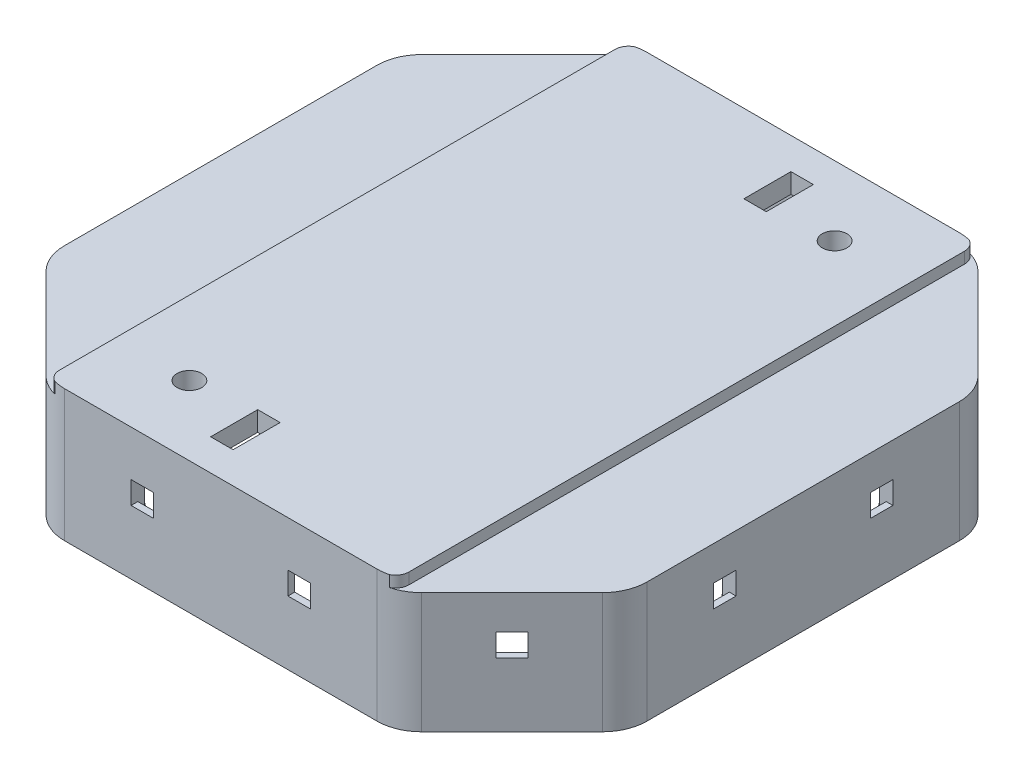
SolidWorks part; units mm, degrees
ref_plane "Front Plane" through (0, 0, 0) normal (0, 0, 1) x (1, 0, 0)
ref_plane "Top Plane" through (0, 0, 0) normal (0, 1, 0) x (1, 0, 0)
ref_plane "Right Plane" through (0, 0, 0) normal (1, 0, 0) x (0, 0, -1)
ref_axis "CenterAxis" through (0, 3.97, 0) along (0, -1, 0)
sketch "Sketch1" plane through (0, 0, 0) normal (0, 1, 0) x (1, 0, 0)
  line L0 (0, 34.664) -> (0, -51.0735) construction
  line L1 (-39, 65) -> (39, 65)
  line L2 (-39, 65) -> (-39, -65)
  line L3 (-39, -65) -> (39, -65)
  line L4 (39, 65) -> (39, -65)
  line L5 (-69.2084, 0) -> (81.5089, 0) construction
  dimension "D1" = 78
  dimension "D2" = 130
extrude "Boss-Extrude1" add sketch "Sketch1" along normal blind 2.5
sketch "Sketch4" plane through (0, 0, 0) normal (0, -1, 0) x (-1, 0, 0)
  line L1 (65, 65) -> (-65, 65)
  line L2 (65, 65) -> (65, -65)
  line L3 (65, -65) -> (-65, -65)
  line L4 (-65, 65) -> (-65, -65)
  line L6 (0, 118.1215) -> (0, -128.1726) construction
  line L7 (153.5171, 0) -> (-213.3352, 0) construction
  dimension "D1" = 130
  dimension "D2" = 130
extrude "Boss-Extrude2" add sketch "Sketch4" along normal blind 1.9
chamfer "Chamfer1" distance 26 angle 45 4 edges at (65, -0.95, 65) (-65, -0.95, 65) (-65, -0.95, -65) (65, -0.95, -65)
sketch "Sketch5" plane through (0, -1.9, 0) normal (0, -1, 0) x (-1, 0, 0)
  line L7 (39, 65) -> (-39, 65) construction
  line L9 (-39, 65) -> (-65, 39) construction
  line L10 (-65, 39) -> (-65, -39) construction
  line L11 (-65, -39) -> (-39, -65) construction
  line L12 (-39, -65) -> (39, -65) construction
  line L13 (39, -65) -> (65, -39) construction
  line L14 (65, -39) -> (65, 39) construction
  line L15 (65, 39) -> (39, 65) construction
  line L16 (39, 65) -> (-39, 65)
  line L17 (-39, 65) -> (-65, 39)
  line L18 (-65, 39) -> (-65, -39)
  line L19 (-65, -39) -> (-39, -65)
  line L20 (-39, -65) -> (39, -65)
  line L21 (39, -65) -> (65, -39)
  line L22 (65, -39) -> (65, 39)
  line L23 (65, 39) -> (39, 65)
  line L24 (37.7574, 62) -> (-37.7574, 62)
  line L25 (-37.7574, 62) -> (-62, 37.7574)
  line L26 (-62, 37.7574) -> (-62, -37.7574)
  line L27 (-62, -37.7574) -> (-37.7574, -62)
  line L28 (-37.7574, -62) -> (37.7574, -62)
  line L29 (37.7574, -62) -> (62, -37.7574)
  line L30 (62, -37.7574) -> (62, 37.7574)
  line L31 (62, 37.7574) -> (37.7574, 62)
  dimension "D1" = 3
extrude "Boss-Extrude3" add sketch "Sketch5" along normal blind 25
sketch "Sketch6" plane through (0, 0, 62) normal (0, 0, -1) x (-1, 0, 0)
  line L0 (0, -73.719) -> (0, 48.5048) construction
  line L1 (-15, -12.65) -> (-20, -12.65)
  line L2 (-15, -12.65) -> (-15, -7.65)
  line L3 (-15, -7.65) -> (-20, -7.65)
  line L4 (-20, -12.65) -> (-20, -7.65)
  line L5 (20, -12.65) -> (15, -12.65)
  line L6 (20, -12.65) -> (20, -7.65)
  line L7 (20, -7.65) -> (15, -7.65)
  line L8 (15, -12.65) -> (15, -7.65)
  line L10 (-37.7574, -1.9) -> (37.7574, -1.9) construction
  dimension "D1" = 5
  dimension "D2" = 5
  dimension "D3" = 5
  dimension "D4" = 5
  dimension "D5" = 30
  dimension "D6" = 5.75
  dimension "D7" = 5.75
extrude "Cut-Extrude3" cut sketch "Sketch6" against normal up to next
sketch "Sketch13" plane through (-49.8787, 0, 49.8787) normal (0.7071, 0, -0.7071) x (-0.7071, 0, -0.7071)
  line L0 (-17.1421, -1.9) -> (17.1421, -1.9) construction
  line L1 (2.5, -12.65) -> (-2.5, -12.65)
  line L2 (2.5, -12.65) -> (2.5, -7.65)
  line L3 (2.5, -7.65) -> (-2.5, -7.65)
  line L4 (-2.5, -12.65) -> (-2.5, -7.65)
  line L5 (0, -31.7169) -> (0, 9.0748) construction
  line L6 (-17.1421, -26.9) -> (-17.1421, -1.9) construction
  line L7 (17.1421, -26.9) -> (17.1421, -1.9) construction
  dimension "D1" = 5
  dimension "D2" = 5
  dimension "D3" = 5.75
extrude "Cut-Extrude6" cut sketch "Sketch13" against normal up to next
sketch "Sketch9" plane through (0, 0, 62) normal (0, 0, -1) x (-1, 0, 0)
  line L0 (39.1927, -10.15) -> (-34.1415, -10.15) construction
  line L4 (20, -18.4) -> (7.35, -18.4)
  line L5 (20, -18.4) -> (20, -1.9)
  line L6 (20, -1.9) -> (7.35, -1.9)
  line L7 (7.35, -18.4) -> (7.35, -1.9)
  line L10 (-20, -18.4) -> (-7.35, -18.4)
  line L11 (-20, -18.4) -> (-20, -1.9)
  line L12 (-20, -1.9) -> (-7.35, -1.9)
  line L13 (-7.35, -18.4) -> (-7.35, -1.9)
  line L18 (-37.7574, -1.9) -> (37.7574, -1.9) construction
  line L19 (20, -12.65) -> (20, -7.65) construction
  line L20 (-20, -7.65) -> (-20, -12.65) construction
  line L21 (20, -7.65) -> (15, -7.65) construction
  line L22 (15, -12.65) -> (20, -12.65) construction
  dimension "D1" = 12.65
  dimension "D2" = 12.65
extrude "Cut-Extrude5" cut sketch "Sketch9" against normal blind 1.5
sketch "Sketch14" plane through (-49.8787, 0, 49.8787) normal (0.7071, 0, -0.7071) x (-0.7071, 0, -0.7071)
  line L0 (-17.1421, -1.9) -> (17.1421, -1.9) construction
  line L1 (2.5, -1.9) -> (-10.15, -1.9)
  line L2 (2.5, -1.9) -> (2.5, -18.4)
  line L3 (2.5, -18.4) -> (-10.15, -18.4)
  line L4 (-10.15, -1.9) -> (-10.15, -18.4)
  line L5 (2.5, -12.65) -> (2.5, -7.65) construction
  line L6 (10.5909, -10.15) -> (-6.85, -10.15) construction
  line L7 (2.5, -7.65) -> (-2.5, -7.65) construction
  line L8 (-2.5, -12.65) -> (2.5, -12.65) construction
  dimension "D1" = 12.65
extrude "Cut-Extrude7" cut sketch "Sketch14" against normal blind 1.5
sketch "Sketch10" plane through (0, 0, 62) normal (0, 0, -1) x (-1, 0, 0)
  line L0 (45.2947, -10.154) -> (11.3128, -10.154) construction
  line L4 (7.35, -18.4) -> (5.35, -18.4)
  line L5 (7.35, -18.4) -> (7.35, -1.9)
  line L6 (7.35, -1.9) -> (5.35, -1.9)
  line L7 (5.35, -18.4) -> (5.35, -1.9)
  line L8 (-7.35, -1.9) -> (7.35, -1.9) construction
  line L9 (-7.35, -18.4) -> (-5.35, -18.4)
  line L10 (-7.35, -18.4) -> (-7.35, -1.9)
  line L11 (-7.35, -1.9) -> (-5.35, -1.9)
  line L12 (-5.35, -18.4) -> (-5.35, -1.9)
  circle A0 centre (22.59, -15.869) radius 1
  circle A1 centre (22.59, -4.439) radius 1
  circle A2 centre (-22.59, -15.869) radius 1
  circle A3 centre (-22.59, -4.439) radius 1
  dimension "D1" = 2
  dimension "D2" = 2
  dimension "D3" = 2
  dimension "D4" = 2
  dimension "D5" = 11.43
  dimension "D6" = 11.43
  dimension "D7" = 8.254
  dimension "D8" = 15.24
  dimension "D9" = 2
  dimension "D10" = 2
  dimension "D11" = 15.24
extrude "Boss-Extrude5" add sketch "Sketch10" along normal blind 1.75
sketch "Sketch15" plane through (-49.8787, 0, 49.8787) normal (0.7071, 0, -0.7071) x (-0.7071, 0, -0.7071)
  line L0 (-17.1421, -1.9) -> (-10.15, -1.9) construction
  line L1 (-10.15, -18.4) -> (-12.15, -18.4)
  line L2 (-10.15, -18.4) -> (-10.15, -1.9)
  line L3 (-10.15, -1.9) -> (-12.15, -1.9)
  line L4 (-12.15, -18.4) -> (-12.15, -1.9)
  line L5 (11.6969, -10.15) -> (-6.9983, -10.15) construction
  line L6 (-2.5, -12.65) -> (2.5, -12.65) construction
  line L7 (2.5, -7.65) -> (-2.5, -7.65) construction
  circle A0 centre (5.09, -15.865) radius 1
  circle A1 centre (5.09, -4.435) radius 1
  dimension "D2" = 2
  dimension "D3" = 2
  dimension "D1" = 2
  dimension "D4" = 15.24
  dimension "D5" = 11.43
extrude "Boss-Extrude9" add sketch "Sketch15" along normal blind 1.75
sketch "Sketch12" plane through (0, -1.9, 0) normal (0, -1, 0) x (-1, 0, 0)
  line L0 (92.5171, 0) -> (-110.2203, 0) construction
  line L1 (32.5, -55) -> (27.5, -55)
  line L2 (32.5, -55) -> (32.5, -50)
  line L3 (32.5, -50) -> (27.5, -50)
  line L4 (27.5, -55) -> (27.5, -50)
  line L5 (0, -112.6882) -> (0, 159.7855) construction
  line L6 (-32.5, -55) -> (-27.5, -55)
  line L7 (-32.5, -55) -> (-32.5, -50)
  line L8 (-32.5, -50) -> (-27.5, -50)
  line L9 (-27.5, -55) -> (-27.5, -50)
  dimension "D1" = 5
  dimension "D2" = 5
  dimension "D3" = 50
  dimension "D4" = 27.5
extrude "Boss-Extrude8" [suppressed] add sketch "Sketch12" along normal blind 10
fillet "Fillet4" [suppressed] radius 1
sketch "Sketch16" plane through (-62, 0, 0) normal (1, 0, 0) x (0, 0, -1)
  line L0 (0, -45.9705) -> (0, 131.7483) construction
  line L1 (20, -12.65) -> (15, -12.65)
  line L2 (20, -12.65) -> (20, -7.65)
  line L3 (20, -7.65) -> (15, -7.65)
  line L4 (15, -12.65) -> (15, -7.65)
  line L5 (-15, -12.65) -> (-20, -12.65)
  line L6 (-15, -12.65) -> (-15, -7.65)
  line L7 (-15, -7.65) -> (-20, -7.65)
  line L8 (-20, -12.65) -> (-20, -7.65)
  line L9 (37.7574, -26.9) -> (37.7574, -1.9) construction
  line L10 (-37.7574, -26.9) -> (-37.7574, -1.9) construction
  line L11 (-37.7574, -1.9) -> (37.7574, -1.9) construction
  dimension "D1" = 30
  dimension "D2" = 5
  dimension "D3" = 5
  dimension "D4" = 5
  dimension "D5" = 5
  dimension "D6" = 5.75
  dimension "D7" = 5.75
extrude "Cut-Extrude8" cut sketch "Sketch16" against normal up to next
sketch "Sketch17" plane through (-62, 0, 0) normal (1, 0, 0) x (0, 0, -1)
  line L0 (20, -12.65) -> (20, -7.65) construction
  line L1 (-15, -18.4) -> (-27.65, -18.4)
  line L2 (-15, -18.4) -> (-15, -1.9)
  line L3 (-15, -1.9) -> (-27.65, -1.9)
  line L4 (-27.65, -18.4) -> (-27.65, -1.9)
  line L5 (20, -18.4) -> (7.35, -18.4)
  line L6 (20, -18.4) -> (20, -1.9)
  line L7 (20, -1.9) -> (7.35, -1.9)
  line L8 (7.35, -18.4) -> (7.35, -1.9)
  line L9 (-37.7574, -1.9) -> (37.7574, -1.9) construction
  line L10 (-15, -12.65) -> (-15, -7.65) construction
  line L11 (27.4384, -10.15) -> (-34.0605, -10.15) construction
  line L12 (15, -12.65) -> (20, -12.65) construction
  line L13 (20, -7.65) -> (15, -7.65) construction
  dimension "D1" = 12.65
  dimension "D2" = 12.65
extrude "Cut-Extrude9" cut sketch "Sketch17" against normal blind 1.5
sketch "Sketch18" plane through (-62, 0, 0) normal (1, 0, 0) x (0, 0, -1)
  line L0 (32.9525, -10.15) -> (-38.3333, -10.15) construction
  line L1 (20, -12.65) -> (15, -12.65) construction
  line L2 (15, -7.65) -> (20, -7.65) construction
  line L3 (7.35, -1.9) -> (7.35, -18.4) construction
  line L4 (-27.65, -1.9) -> (-27.65, -18.4) construction
  line L5 (-15, -1.9) -> (7.35, -1.9) construction
  line L6 (7.35, -18.4) -> (5.35, -18.4)
  line L7 (7.35, -18.4) -> (7.35, -1.9)
  line L8 (7.35, -1.9) -> (5.35, -1.9)
  line L9 (5.35, -18.4) -> (5.35, -1.9)
  line L10 (-37.7574, -1.9) -> (-27.65, -1.9) construction
  line L11 (-27.65, -18.4) -> (-29.65, -18.4)
  line L12 (-27.65, -18.4) -> (-27.65, -1.9)
  line L13 (-27.65, -1.9) -> (-29.65, -1.9)
  line L14 (-29.65, -18.4) -> (-29.65, -1.9)
  circle A0 centre (22.59, -15.865) radius 1
  circle A1 centre (22.59, -4.435) radius 1
  circle A2 centre (-12.41, -15.865) radius 1
  circle A3 centre (-12.41, -4.435) radius 1
  dimension "D3" = 2
  dimension "D4" = 2
  dimension "D5" = 2
  dimension "D6" = 2
  dimension "D1" = 11.43
  dimension "D2" = 11.43
  dimension "D7" = 15.24
  dimension "D8" = 15.24
  dimension "D9" = 2
  dimension "D10" = 2
extrude "Boss-Extrude10" add sketch "Sketch18" along normal blind 1.75
sketch "Sketch19" plane through (49.8787, 0, 49.8787) normal (-0.7071, 0, -0.7071) x (-0.7071, 0, 0.7071)
  line L0 (0, -22.7201) -> (0, -10.1184) construction
  line L3 (17.1421, -26.9) -> (17.1421, -1.9) construction
  line L4 (-17.1421, -26.9) -> (-17.1421, -1.9) construction
  line L5 (-17.1421, -1.9) -> (17.1421, -1.9) construction
  line L6 (2.5, -12.65) -> (-2.5, -12.65)
  line L7 (2.5, -12.65) -> (2.5, -7.65)
  line L8 (2.5, -7.65) -> (-2.5, -7.65)
  line L9 (-2.5, -12.65) -> (-2.5, -7.65)
  dimension "D1" = 5
  dimension "D2" = 5
  dimension "D3" = 5.75
extrude "Cut-Extrude10" cut sketch "Sketch19" against normal up to next
sketch "Sketch20" plane through (49.8787, 0, 49.8787) normal (-0.7071, 0, -0.7071) x (-0.7071, 0, 0.7071)
  line L0 (-17.1421, -1.9) -> (17.1421, -1.9) construction
  line L1 (10.15, -18.4) -> (-2.5, -18.4)
  line L2 (10.15, -18.4) -> (10.15, -1.9)
  line L3 (10.15, -1.9) -> (-2.5, -1.9)
  line L4 (-2.5, -18.4) -> (-2.5, -1.9)
  line L5 (-2.5, -7.65) -> (-2.5, -12.65) construction
  line L6 (13.9228, -10.15) -> (-12.316, -10.15) construction
  line L7 (-2.5, -12.65) -> (2.5, -12.65) construction
  line L8 (2.5, -7.65) -> (-2.5, -7.65) construction
  dimension "D1" = 12.65
extrude "Cut-Extrude11" cut sketch "Sketch20" against normal blind 1.5
sketch "Sketch21" plane through (49.8787, 0, 49.8787) normal (-0.7071, 0, -0.7071) x (-0.7071, 0, 0.7071)
  line L0 (15.0556, -10.15) -> (-12.6108, -10.15) construction
  line L1 (12.15, -18.4) -> (10.15, -18.4)
  line L2 (12.15, -18.4) -> (12.15, -1.9)
  line L3 (12.15, -1.9) -> (10.15, -1.9)
  line L4 (10.15, -18.4) -> (10.15, -1.9)
  line L5 (2.5, -12.65) -> (-2.5, -12.65) construction
  line L6 (-2.5, -7.65) -> (2.5, -7.65) construction
  line L7 (10.15, -1.9) -> (17.1421, -1.9) construction
  circle A0 centre (-5.09, -15.865) radius 1
  circle A1 centre (-5.09, -4.435) radius 1
  dimension "D1" = 2
  dimension "D2" = 2
  dimension "D3" = 2
  dimension "D4" = 15.24
  dimension "D5" = 11.43
extrude "Boss-Extrude11" add sketch "Sketch21" along normal blind 1.75
sketch "Sketch22" plane through (62, 0, 0) normal (-1, 0, 0) x (0, 0, 1)
  line L0 (0, -48.3456) -> (0, 13.9543) construction
  line L1 (20, -12.65) -> (15, -12.65)
  line L2 (20, -12.65) -> (20, -7.65)
  line L3 (20, -7.65) -> (15, -7.65)
  line L4 (15, -12.65) -> (15, -7.65)
  line L5 (-15, -12.65) -> (-20, -12.65)
  line L6 (-15, -12.65) -> (-15, -7.65)
  line L7 (-15, -7.65) -> (-20, -7.65)
  line L8 (-20, -12.65) -> (-20, -7.65)
  line L9 (37.7574, -26.9) -> (37.7574, -1.9) construction
  line L10 (-37.7574, -26.9) -> (-37.7574, -1.9) construction
  line L12 (-37.7574, -1.9) -> (37.7574, -1.9) construction
  dimension "D1" = 5
  dimension "D2" = 5
  dimension "D3" = 5
  dimension "D4" = 5
  dimension "D5" = 5.75
  dimension "D6" = 5.75
  dimension "D7" = 30
extrude "Cut-Extrude12" cut sketch "Sketch22" against normal up to next
sketch "Sketch23" plane through (62, 0, 0) normal (-1, 0, 0) x (0, 0, 1)
  line L1 (27.65, -18.4) -> (15, -18.4)
  line L2 (27.65, -18.4) -> (27.65, -1.9)
  line L3 (27.65, -1.9) -> (15, -1.9)
  line L4 (15, -18.4) -> (15, -1.9)
  line L5 (-7.35, -18.4) -> (-20, -18.4)
  line L6 (-7.35, -18.4) -> (-7.35, -1.9)
  line L7 (-7.35, -1.9) -> (-20, -1.9)
  line L8 (-20, -18.4) -> (-20, -1.9)
  line L10 (-37.7574, -1.9) -> (37.7574, -1.9) construction
  line L11 (30.5276, -10.15) -> (-34.6722, -10.15) construction
  line L12 (20, -7.65) -> (15, -7.65) construction
  line L13 (15, -12.65) -> (20, -12.65) construction
  line L14 (15, -7.65) -> (15, -12.65) construction
  line L15 (-20, -7.65) -> (-20, -12.65) construction
  dimension "D1" = 12.65
  dimension "D2" = 12.65
extrude "Cut-Extrude13" cut sketch "Sketch23" against normal blind 1.5
sketch "Sketch24" plane through (62, 0, 0) normal (-1, 0, 0) x (0, 0, 1)
  line L0 (29.9106, -10.15) -> (-34.7522, -10.15) construction
  line L1 (29.65, -18.4) -> (27.65, -18.4)
  line L2 (29.65, -18.4) -> (29.65, -1.9)
  line L3 (29.65, -1.9) -> (27.65, -1.9)
  line L4 (27.65, -18.4) -> (27.65, -1.9)
  line L5 (-5.35, -18.4) -> (-7.35, -18.4)
  line L6 (-5.35, -18.4) -> (-5.35, -1.9)
  line L7 (-5.35, -1.9) -> (-7.35, -1.9)
  line L8 (-7.35, -18.4) -> (-7.35, -1.9)
  line L9 (20, -12.65) -> (15, -12.65) construction
  line L10 (15, -7.65) -> (20, -7.65) construction
  line L11 (-7.35, -1.9) -> (15, -1.9) construction
  line L12 (27.65, -1.9) -> (37.7574, -1.9) construction
  circle A0 centre (12.41, -15.865) radius 1
  circle A1 centre (12.41, -4.435) radius 1
  circle A2 centre (-22.59, -15.865) radius 1
  circle A3 centre (-22.59, -4.435) radius 1
  dimension "D1" = 2
  dimension "D2" = 2
  dimension "D3" = 2
  dimension "D4" = 2
  dimension "D5" = 2
  dimension "D6" = 2
  dimension "D7" = 15.24
  dimension "D8" = 15.24
  dimension "D9" = 11.43
  dimension "D10" = 11.43
extrude "Boss-Extrude12" add sketch "Sketch24" along normal blind 1.75
sketch "Sketch27" plane through (0, -1.9, 0) normal (0, -1, 0) x (-1, 0, 0)
  line L0 (-25.75, 57) -> (-9.25, 57)
  line L3 (37.7574, 62) -> (-37.7574, 62) construction
  line L4 (-9.25, 62) -> (-25.75, 62)
  line L5 (25.75, 62) -> (25.75, 57)
  line L6 (-9.25, 62) -> (-9.25, 57)
  line L7 (-25.75, 57) -> (-25.75, 62)
  line L8 (9.25, 62) -> (9.25, 57)
  line L9 (9.25, 57) -> (25.75, 57)
  line L10 (9.25, 62) -> (25.75, 62)
  line L11 (0, 103.5595) -> (0, 19.1897) construction
  dimension "D1" = 16.5
  dimension "D2" = 18.5
  dimension "D4" = 16.5
  dimension "D5" = 5
  dimension "D6" = 5
extrude "Cut-Extrude16" cut sketch "Sketch27" against normal up to surface (1.9 mm away) up to face at (-52, 0, -22.75)
sketch "Sketch32" plane through (0, 0, -62) normal (0, 0, 1) x (1, 0, 0)
  line L0 (0, -56.2842) -> (0, 5.1948) construction
  line L1 (20, -12.65) -> (15, -12.65)
  line L2 (20, -12.65) -> (20, -7.65)
  line L3 (20, -7.65) -> (15, -7.65)
  line L4 (15, -12.65) -> (15, -7.65)
  line L5 (-15, -12.65) -> (-20, -12.65)
  line L6 (-15, -12.65) -> (-15, -7.65)
  line L7 (-15, -7.65) -> (-20, -7.65)
  line L8 (-20, -12.65) -> (-20, -7.65)
  line L9 (-37.7574, -26.9) -> (-37.7574, -1.9) construction
  line L10 (37.7574, -26.9) -> (37.7574, -1.9) construction
  line L11 (-37.7574, 0) -> (37.7574, 0) construction
  dimension "D1" = 5
  dimension "D2" = 5
  dimension "D3" = 5
  dimension "D4" = 5
  dimension "D5" = 30
  dimension "D6" = 7.65
  dimension "D7" = 7.65
extrude "Cut-Extrude20" cut sketch "Sketch32" against normal up to next
sketch "Sketch33" plane through (0, 0, -62) normal (0, 0, 1) x (1, 0, 0)
  line L0 (15, -12.65) -> (20, -12.65) construction
  line L1 (25.75, -12.65) -> (9.25, -12.65)
  line L2 (25.75, -12.65) -> (25.75, 0)
  line L3 (25.75, 0) -> (9.25, 0)
  line L4 (9.25, -12.65) -> (9.25, 0)
  line L5 (17.5, -39.4676) -> (17.5, 3.7001) construction
  line L6 (-17.5, -41.1802) -> (-17.5, 6.7675) construction
  line L7 (15, -7.65) -> (15, -12.65) construction
  line L8 (20, -12.65) -> (20, -7.65) construction
  line L9 (-15, -12.65) -> (-15, -7.65) construction
  line L10 (-20, -7.65) -> (-20, -12.65) construction
  line L11 (-20, -12.65) -> (-15, -12.65) construction
  line L12 (-9.25, -12.65) -> (-25.75, -12.65)
  line L13 (-9.25, -12.65) -> (-9.25, 0)
  line L14 (-9.25, 0) -> (-25.75, 0)
  line L15 (-25.75, -12.65) -> (-25.75, 0)
  dimension "D1" = 12.65
  dimension "D2" = 16.5
  dimension "D3" = 12.65
  dimension "D4" = 16.5
extrude "Cut-Extrude21" cut sketch "Sketch33" against normal blind 1.5
sketch "Sketch34" plane through (0, 0, -62) normal (0, 0, 1) x (1, 0, 0)
  line L0 (17.5, 6.692) -> (17.5, -45.6178) construction
  line L1 (20, -7.65) -> (20, -12.65) construction
  line L2 (15, -12.65) -> (15, -7.65) construction
  line L4 (-17.5, -39.3596) -> (-17.5, 3.7236) construction
  line L5 (-15, -7.65) -> (-15, -12.65) construction
  line L6 (-20, -12.65) -> (-20, -7.65) construction
  line L10 (25.75, 0) -> (9.25, 0) construction
  line L11 (-9.25, 0) -> (-25.75, 0) construction
  circle A0 centre (23.215, -15.24) radius 1
  circle A1 centre (11.785, -15.24) radius 1
  circle A2 centre (-11.785, -15.24) radius 1
  circle A3 centre (-23.215, -15.24) radius 1
  dimension "D1" = 2
  dimension "D2" = 2
  dimension "D5" = 2
  dimension "D6" = 2
  dimension "D3" = 11.43
  dimension "D4" = 15.24
  dimension "D7" = 11.43
  dimension "D8" = 15.24
extrude "Boss-Extrude14" add sketch "Sketch34" along normal blind 1.75
sketch "Sketch35" plane through (49.8787, 0, -49.8787) normal (-0.7071, 0, 0.7071) x (0.7071, 0, 0.7071)
  line L0 (-17.1421, -1.9) -> (17.1421, -1.9) construction
  line L1 (2.5, -12.65) -> (-2.5, -12.65)
  line L2 (2.5, -12.65) -> (2.5, -7.65)
  line L3 (2.5, -7.65) -> (-2.5, -7.65)
  line L4 (-2.5, -12.65) -> (-2.5, -7.65)
  line L5 (0, -41.1131) -> (0, 9.0774) construction
  line L6 (17.1421, -26.9) -> (17.1421, -1.9) construction
  line L7 (-17.1421, -26.9) -> (-17.1421, -1.9) construction
  dimension "D1" = 5
  dimension "D2" = 5
  dimension "D3" = 5.75
extrude "Cut-Extrude22" cut sketch "Sketch35" against normal up to next
sketch "Sketch36" plane through (49.8787, 0, -49.8787) normal (-0.7071, 0, 0.7071) x (0.7071, 0, 0.7071)
  line L0 (-2.5, -7.65) -> (-2.5, -12.65) construction
  line L1 (10.15, -1.9) -> (-2.5, -1.9)
  line L2 (10.15, -1.9) -> (10.15, -18.4)
  line L3 (10.15, -18.4) -> (-2.5, -18.4)
  line L4 (-2.5, -1.9) -> (-2.5, -18.4)
  line L5 (14.9901, -10.15) -> (-10.7496, -10.15) construction
  line L6 (-2.5, -12.65) -> (2.5, -12.65) construction
  line L7 (2.5, -7.65) -> (-2.5, -7.65) construction
  line L8 (-17.1421, -1.9) -> (17.1421, -1.9) construction
  dimension "D1" = 12.65
extrude "Cut-Extrude23" cut sketch "Sketch36" against normal blind 1.5
sketch "Sketch37" plane through (49.8787, 0, -49.8787) normal (-0.7071, 0, 0.7071) x (0.7071, 0, 0.7071)
  line L0 (10.15, -1.9) -> (17.1421, -1.9) construction
  line L1 (10.15, -18.4) -> (12.15, -18.4)
  line L2 (10.15, -18.4) -> (10.15, -1.9)
  line L3 (10.15, -1.9) -> (12.15, -1.9)
  line L4 (12.15, -18.4) -> (12.15, -1.9)
  line L5 (15.4954, -10.15) -> (-15.257, -10.15) construction
  line L6 (2.5, -7.65) -> (-2.5, -7.65) construction
  line L7 (-2.5, -12.65) -> (2.5, -12.65) construction
  circle A0 centre (-5.09, -15.865) radius 1
  circle A1 centre (-5.09, -4.435) radius 1
  dimension "D2" = 2
  dimension "D3" = 2
  dimension "D1" = 2
  dimension "D4" = 11.43
  dimension "D5" = 15.24
extrude "Boss-Extrude15" add sketch "Sketch37" along normal blind 1.75
fillet "Fillet5" radius 3 4 edges tangent propagation no
sketch "Sketch38" plane through (-49.8787, 0, -49.8787) normal (0.7071, 0, 0.7071) x (0.7071, 0, -0.7071)
  line L0 (0, -45.2412) -> (0, 20.7133) construction
  line L1 (-17.1421, -26.9) -> (-17.1421, -1.9) construction
  line L2 (17.1421, -26.9) -> (17.1421, -1.9) construction
  line L3 (-17.1421, -1.9) -> (17.1421, -1.9) construction
  line L4 (2.5, -12.65) -> (-2.5, -12.65)
  line L5 (2.5, -12.65) -> (2.5, -7.65)
  line L6 (2.5, -7.65) -> (-2.5, -7.65)
  line L7 (-2.5, -12.65) -> (-2.5, -7.65)
  dimension "D1" = 5
  dimension "D2" = 5
  dimension "D3" = 5.75
extrude "Cut-Extrude24" cut sketch "Sketch38" against normal up to next contours L6 L7 L4 L5
sketch "Sketch39" plane through (-49.8787, 0, -49.8787) normal (0.7071, 0, 0.7071) x (0.7071, 0, -0.7071)
  line L0 (2.5, -12.65) -> (2.5, -7.65) construction
  line L1 (2.5, -18.4) -> (-10.15, -18.4)
  line L2 (2.5, -18.4) -> (2.5, -1.9)
  line L3 (2.5, -1.9) -> (-10.15, -1.9)
  line L4 (-10.15, -18.4) -> (-10.15, -1.9)
  line L5 (-17.1421, -1.9) -> (17.1421, -1.9) construction
  line L6 (7.9642, -10.15) -> (-14.3354, -10.15) construction
  line L7 (2.5, -7.65) -> (-2.5, -7.65) construction
  line L8 (2.5, -12.65) -> (-2.5, -12.65) construction
  dimension "D1" = 12.65
extrude "Cut-Extrude25" cut sketch "Sketch39" against normal blind 1.5
sketch "Sketch40" plane through (-49.8787, 0, -49.8787) normal (0.7071, 0, 0.7071) x (0.7071, 0, -0.7071)
  line L0 (-17.1421, -1.9) -> (-10.15, -1.9) construction
  line L1 (-10.15, -18.4) -> (-12.15, -18.4)
  line L2 (-10.15, -18.4) -> (-10.15, -1.9)
  line L3 (-10.15, -1.9) -> (-12.15, -1.9)
  line L4 (-12.15, -18.4) -> (-12.15, -1.9)
  line L5 (11.3212, -10.15) -> (-14.9762, -10.15) construction
  line L6 (-2.5, -12.65) -> (2.5, -12.65) construction
  line L7 (-2.5, -7.65) -> (2.5, -7.65) construction
  circle A0 centre (5.09, -15.865) radius 1
  circle A1 centre (5.09, -4.435) radius 1
  dimension "D2" = 2
  dimension "D3" = 2
  dimension "D1" = 2
  dimension "D4" = 11.43
  dimension "D5" = 15.24
extrude "Boss-Extrude16" add sketch "Sketch40" along normal blind 1.75
fillet "Fillet6" radius 10 8 edges at (-65, -13.45, -39) (65, -13.45, -39) (65, -13.45, 39) (-65, -13.45, 39)
sketch "Sketch41" plane through (0, -1.9, 0) normal (0, -1, 0) x (-1, 0, 0)
  line L0 (-49.9494, -39.5549) -> (-51.7172, -37.7872)
  line L1 (-51.7172, -37.7872) -> (-49.9494, -36.0194)
  line L2 (-49.9494, -36.0194) -> (-48.1816, -37.7872)
  line L3 (-48.1816, -37.7872) -> (-49.9494, -39.5549)
  line L4 (-43.7622, -58.1165) -> (-41.4641, -55.8184) construction
  line L5 (-40.0499, -57.2326) -> (-41.4641, -55.8184) construction
  line L6 (37.7872, 51.7172) -> (39.5549, 49.9494)
  line L7 (-27.35, -52.25) -> (-24.85, -52.25)
  line L8 (-27.35, -52.25) -> (-27.35, -54.75)
  line L9 (-27.35, -54.75) -> (-24.85, -54.75)
  line L10 (-24.85, -52.25) -> (-24.85, -54.75)
  line L11 (24.85, -52.25) -> (27.35, -52.25)
  line L12 (24.85, -52.25) -> (24.85, -54.75)
  line L13 (24.85, -54.75) -> (27.35, -54.75)
  line L14 (27.35, -52.25) -> (27.35, -54.75)
  line L15 (52.25, -7.65) -> (54.75, -7.65)
  line L16 (52.25, -7.65) -> (52.25, -10.15)
  line L17 (52.25, -10.15) -> (54.75, -10.15)
  line L18 (54.75, -7.65) -> (54.75, -10.15)
  line L19 (52.25, 27.35) -> (54.75, 27.35)
  line L20 (52.25, 27.35) -> (52.25, 24.85)
  line L21 (52.25, 24.85) -> (54.75, 24.85)
  line L22 (54.75, 27.35) -> (54.75, 24.85)
  line L23 (-54.75, -7.65) -> (-52.25, -7.65)
  line L24 (-54.75, -7.65) -> (-54.75, -10.15)
  line L25 (-54.75, -10.15) -> (-52.25, -10.15)
  line L26 (-52.25, -7.65) -> (-52.25, -10.15)
  line L27 (-54.75, 27.35) -> (-52.25, 27.35)
  line L28 (-54.75, 27.35) -> (-54.75, 24.85)
  line L29 (-54.75, 24.85) -> (-52.25, 24.85)
  line L30 (-52.25, 27.35) -> (-52.25, 24.85)
  line L31 (39.5549, 49.9494) -> (37.7872, 48.1816)
  line L32 (37.7872, 48.1816) -> (36.0194, 49.9494)
  line L33 (36.0194, 49.9494) -> (37.7872, 51.7172)
  line L34 (-39.5549, 49.9494) -> (-37.7872, 48.1816)
  line L35 (-37.7872, 48.1816) -> (-36.0194, 49.9494)
  line L36 (-36.0194, 49.9494) -> (-37.7872, 51.7172)
  line L37 (-37.7872, 51.7172) -> (-39.5549, 49.9494)
  line L38 (-5.35, -60.25) -> (-7.35, -60.25) construction
  line L39 (-7.35, -63.5) -> (-7.35, -60.25) construction
  line L40 (7.35, -60.25) -> (7.35, -62) construction
  line L41 (5.35, -60.25) -> (7.35, -60.25) construction
  line L42 (51.7172, -37.7872) -> (49.9494, -39.5549)
  line L43 (49.9494, -39.5549) -> (48.1816, -37.7872)
  line L44 (48.1816, -37.7872) -> (49.9494, -36.0194)
  line L45 (49.9494, -36.0194) -> (51.7172, -37.7872)
  line L48 (41.4641, -55.8184) -> (40.0499, -57.2326) construction
  line L49 (43.7622, -58.1165) -> (41.4641, -55.8184) construction
  line L50 (-60.25, -27.65) -> (-62, -27.65) construction
  line L51 (-60.25, -29.65) -> (-60.25, -27.65) construction
  line L52 (-60.25, 7.35) -> (-62, 7.35) construction
  line L53 (-60.25, 5.35) -> (-60.25, 7.35) construction
  line L54 (-58.1165, 43.7622) -> (-55.8184, 41.4641) construction
  line L55 (-57.2326, 40.0499) -> (-55.8184, 41.4641) construction
  line L56 (-55.8184, 41.4641) -> (-57.0558, 42.7015) construction
  line L57 (-55.8184, 41.4641) -> (-57.2326, 40.0499) construction
  line L58 (60.25, -27.65) -> (62, -27.65) construction
  line L59 (60.25, -29.65) -> (60.25, -27.65) construction
  line L60 (60.25, 7.35) -> (62, 7.35) construction
  line L61 (60.25, 5.35) -> (60.25, 7.35) construction
  line L64 (58.1165, 43.7622) -> (55.8184, 41.4641) construction
  line L65 (57.2326, 40.0499) -> (55.8184, 41.4641) construction
  dimension "D1" = 17.5
  dimension "D2" = 5.5
  dimension "D3" = 2.5
  dimension "D4" = 2.5
  dimension "D5" = 5.5
  dimension "D6" = 17.5
  dimension "D7" = 2.5
  dimension "D8" = 2.5
  dimension "D9" = 17.5
  dimension "D10" = 5.5
  dimension "D11" = 2.5
  dimension "D12" = 2.5
  dimension "D13" = 5.5
  dimension "D14" = 17.5
  dimension "D15" = 2.5
  dimension "D16" = 2.5
  dimension "D17" = 17.5
  dimension "D18" = 5.5
  dimension "D19" = 2.5
  dimension "D20" = 2.5
  dimension "D21" = 17.5
  dimension "D22" = 5.5
  dimension "D23" = 2.5
  dimension "D24" = 2.5
  dimension "D25" = 17.5
  dimension "D26" = 5.5
  dimension "D27" = 2.5
  dimension "D28" = 2.5
  dimension "D29" = 17.5
  dimension "D30" = 5.5
  dimension "D31" = 2.5
  dimension "D32" = 2.5
  dimension "D33" = 17.5
  dimension "D34" = 5.5
  dimension "D35" = 2.5
  dimension "D36" = 2.5
  dimension "D37" = 17.5
  dimension "D38" = 5.5
  dimension "D39" = 2.5
  dimension "D40" = 2.5
extrude "Boss-Extrude17" add sketch "Sketch41" along normal blind 5
sketch "Sketch42" plane through (0, 0, -62) normal (0, 0, 1) x (1, 0, 0)
  line L0 (25.75, -12.65) -> (25.75, -1.9) construction
  line L1 (30.75, -21.5) -> (26.75, -21.5)
  line L2 (30.75, -21.5) -> (30.75, -17.5)
  line L3 (30.75, -17.5) -> (26.75, -17.5)
  line L4 (26.75, -21.5) -> (26.75, -17.5)
  line L5 (-26.75, -21.5) -> (-30.75, -21.5)
  line L6 (-26.75, -21.5) -> (-26.75, -17.5)
  line L7 (-26.75, -17.5) -> (-30.75, -17.5)
  line L8 (-30.75, -21.5) -> (-30.75, -17.5)
  line L10 (-25.75, -1.9) -> (-25.75, -12.65) construction
  line L12 (-9.25, 0) -> (-25.75, 0) construction
  line L13 (25.75, 0) -> (9.25, 0) construction
  dimension "D1" = 4
  dimension "D2" = 4
  dimension "D3" = 4
  dimension "D4" = 4
  dimension "D5" = 1
  dimension "D6" = 17.5
  dimension "D7" = 1
  dimension "D8" = 17.5
extrude "Boss-Extrude18" add sketch "Sketch42" along normal blind 12
sketch "Sketch43" plane through (26.75, 0, 0) normal (-1, 0, 0) x (0, 0, 1)
  line L0 (-50, -17.5) -> (-62, -17.5) construction
  line L1 (-50, -21.5) -> (-54, -21.5)
  line L2 (-50, -21.5) -> (-50, -17.5)
  line L3 (-50, -17.5) -> (-54, -17.5)
  line L4 (-54, -21.5) -> (-54, -17.5)
  dimension "D1" = 4
extrude "Boss-Extrude19" add sketch "Sketch43" along normal blind 10
sketch "Sketch44" plane through (-26.75, 0, 0) normal (1, 0, 0) x (0, 0, -1)
  line L0 (50, -17.5) -> (62, -17.5) construction
  line L1 (50, -21.5) -> (54, -21.5)
  line L2 (50, -21.5) -> (50, -17.5)
  line L3 (50, -17.5) -> (54, -17.5)
  line L4 (54, -21.5) -> (54, -17.5)
  dimension "D1" = 4
extrude "Boss-Extrude20" add sketch "Sketch44" along normal blind 10
fillet "Fillet8" radius 0.75 120 edges at (54.75, -6.9, -26.1) (54.75, -1.9, -26.1) (54.75, -4.4, -24.85) (53.5, -6.9, -24.85) (53.5, -1.9, -24.85) (52.25, -4.4, -24.85) (52.25, -6.9, -26.1) (52.25, -1.9, -26.1) (52.25, -4.4, -27.35) (53.5, -6.9, -27.35) (54.75, -4.4, -27.35) (53.5, -1.9, -27.35) (38.671, -6.9, -50.8333) (38.671, -1.9, -50.8333) (39.5549, -4.4, -49.9494) (38.671, -6.9, -49.0655) (38.671, -1.9, -49.0655) (37.7872, -4.4, -48.1816) (36.9033, -6.9, -49.0655) (36.9033, -1.9, -49.0655) (36.0194, -4.4, -49.9494) (36.9033, -6.9, -50.8333) (37.7872, -4.4, -51.7172) (36.9033, -1.9, -50.8333) (-38.671, -6.9, -50.8333) (-38.671, -1.9, -50.8333) (-37.7872, -4.4, -51.7172) (-36.9033, -6.9, -50.8333) (-36.9033, -1.9, -50.8333) (-36.0194, -4.4, -49.9494) (-36.9033, -6.9, -49.0655) (-36.9033, -1.9, -49.0655) (-37.7872, -4.4, -48.1816) (-38.671, -6.9, -49.0655) (-39.5549, -4.4, -49.9494) (-38.671, -1.9, -49.0655) (-54.75, -6.9, -26.1) (-54.75, -1.9, -26.1) (-54.75, -4.4, -27.35) (-53.5, -6.9, -27.35) (-53.5, -1.9, -27.35) (-53.5, -6.9, -24.85) (-54.75, -4.4, -24.85) (-53.5, -1.9, -24.85) (-52.25, -4.4, -27.35) (-52.25, -6.9, -26.1) (-52.25, -4.4, -24.85) (-52.25, -1.9, -26.1) (-54.75, -6.9, 8.9) (-54.75, -1.9, 8.9) (-53.5, -6.9, 10.15) (-54.75, -4.4, 10.15) (-53.5, -1.9, 10.15) (-54.75, -4.4, 7.65) (-53.5, -6.9, 7.65) (-53.5, -1.9, 7.65) (-52.25, -4.4, 7.65) (-52.25, -6.9, 8.9) (-52.25, -4.4, 10.15) (-52.25, -1.9, 8.9) (-49.0655, -6.9, 36.9033) (-49.0655, -1.9, 36.9033) (-50.8333, -6.9, 36.9033) (-49.9494, -4.4, 36.0194) (-50.8333, -1.9, 36.9033) (-50.8333, -6.9, 38.671) (-51.7172, -4.4, 37.7872) (-50.8333, -1.9, 38.671) (-48.1816, -4.4, 37.7872) (-49.0655, -6.9, 38.671) (-49.9494, -4.4, 39.5549) (-49.0655, -1.9, 38.671) (-26.1, -6.9, 54.75) (-26.1, -1.9, 54.75) (-27.35, -4.4, 54.75) (-27.35, -6.9, 53.5) (-27.35, -1.9, 53.5) (-27.35, -4.4, 52.25) (-26.1, -6.9, 52.25) (-26.1, -1.9, 52.25) (-24.85, -4.4, 52.25) (-24.85, -6.9, 53.5) (-24.85, -4.4, 54.75) (-24.85, -1.9, 53.5) (26.1, -6.9, 52.25) (26.1, -1.9, 52.25) (24.85, -6.9, 53.5) (24.85, -4.4, 52.25) (24.85, -1.9, 53.5) (26.1, -6.9, 54.75) (24.85, -4.4, 54.75) (26.1, -1.9, 54.75) (27.35, -4.4, 52.25) (27.35, -6.9, 53.5) (27.35, -4.4, 54.75) (27.35, -1.9, 53.5) (53.5, -6.9, 10.15) (53.5, -1.9, 10.15) (52.25, -4.4, 10.15) (52.25, -6.9, 8.9) (52.25, -1.9, 8.9) (52.25, -4.4, 7.65) (53.5, -6.9, 7.65) (53.5, -1.9, 7.65) (54.75, -4.4, 7.65) (54.75, -6.9, 8.9) (54.75, -4.4, 10.15) (54.75, -1.9, 8.9) (50.8333, -6.9, 38.671) (50.8333, -1.9, 38.671) (49.9494, -4.4, 39.5549) (49.0655, -6.9, 38.671) (49.0655, -1.9, 38.671) (48.1816, -4.4, 37.7872) (49.0655, -6.9, 36.9033) (49.0655, -1.9, 36.9033) (49.9494, -4.4, 36.0194) (50.8333, -6.9, 36.9033) (51.7172, -4.4, 37.7872) (50.8333, -1.9, 36.9033)
fillet "Fillet9" radius 0.75 36 edges at (-28.75, -17.5, -62) (-28.75, -21.5, -62) (-30.75, -17.5, -56) (-30.75, -21.5, -56) (-30.75, -19.5, -62) (-30.75, -19.5, -50) (-23.75, -17.5, -50) (-23.75, -21.5, -50) (-16.75, -17.5, -52) (-16.75, -21.5, -52) (-16.75, -19.5, -50) (-21.75, -21.5, -54) (-16.75, -19.5, -54) (-21.75, -17.5, -54) (-26.75, -17.5, -58) (-26.75, -19.5, -62) (-26.75, -21.5, -58) (-26.75, -19.5, -54) (26.75, -19.5, -62) (26.75, -19.5, -54) (30.75, -19.5, -62) (30.75, -19.5, -50) (16.75, -19.5, -54) (16.75, -19.5, -50) (30.75, -17.5, -56) (23.75, -17.5, -50) (16.75, -17.5, -52) (21.75, -17.5, -54) (26.75, -17.5, -58) (28.75, -17.5, -62) (26.75, -21.5, -58) (21.75, -21.5, -54) (16.75, -21.5, -52) (23.75, -21.5, -50) (30.75, -21.5, -56) (28.75, -21.5, -62)
sketch "Sketch46" plane through (0, -1.9, 0) normal (0, -1, 0) x (1, 0, 0)
  line L1 (4.25, -47.5) -> (9.25, -47.5)
  line L2 (4.25, -47.5) -> (4.25, -58)
  line L3 (4.25, -58) -> (9.25, -58)
  line L4 (9.25, -47.5) -> (9.25, -58)
  line L13 (-9.25, 58) -> (-9.25, 47.5)
  line L14 (-4.25, 58) -> (-9.25, 58)
  line L15 (-4.25, 47.5) -> (-4.25, 58)
  line L16 (-9.25, 47.5) -> (-4.25, 47.5)
  dimension "D1" = 47.5
  dimension "D2" = 4.25
  dimension "D3" = 5
  dimension "D4" = 10.5
  dimension "D5" = 5
  dimension "D6" = 10.5
  dimension "D7" = 47.5
  dimension "D8" = 4.25
extrude "Cut-Extrude27" cut sketch "Sketch46" against normal up to next
sketch "Sketch47" plane through (0, -1.9, 0) normal (0, -1, 0) x (-1, 0, 0)
  circle A1 centre (-22.5, 49.5) radius 2.75
  circle A3 centre (22.5, -49.5) radius 2.75
  dimension "D3" = 5.5
  dimension "D6" = 5.5
  dimension "D1" = 22.5
  dimension "D2" = 49.5
  dimension "D4" = 49.5
  dimension "D5" = 22.5
extrude "Cut-Extrude28" cut sketch "Sketch47" against normal through all
